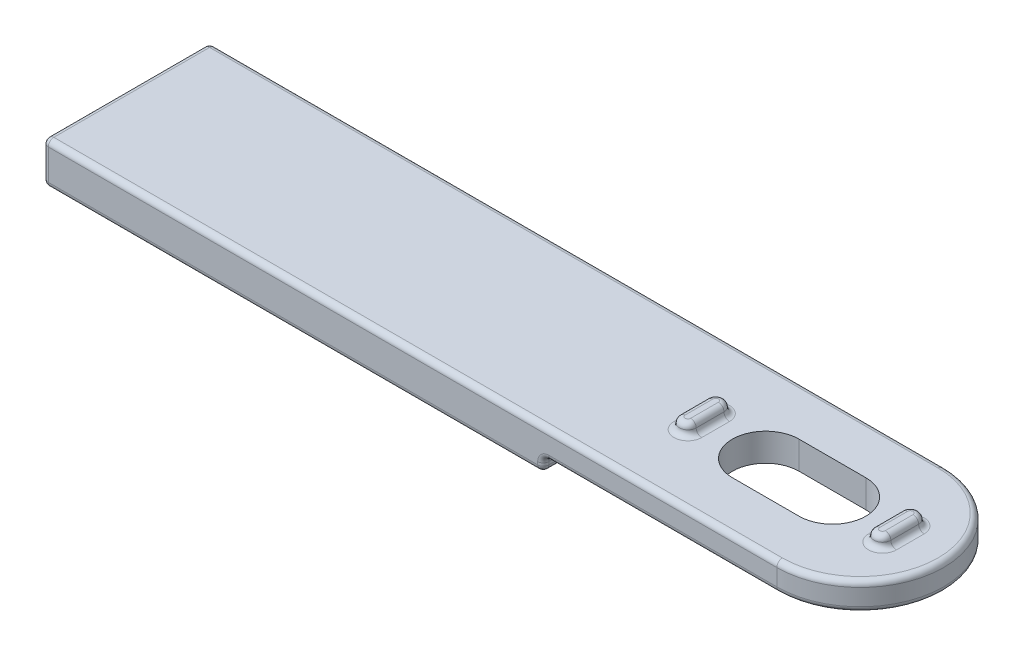
SolidWorks part; units mm, degrees
material "1.0070 (E360)"
ref_plane "Płaszczyzna przednia" through (0, 0, 0) normal (0, 0, 1) x (1, 0, 0)
ref_plane "Płaszczyzna górna" through (0, 0, 0) normal (0, 1, 0) x (1, 0, 0)
ref_plane "Płaszczyzna prawa" through (0, 0, 0) normal (1, 0, 0) x (0, 0, -1)
sketch "Szkic6" plane through (0, 0, -30) normal (0, 1, 0) x (-1, 0, 0)
  line L0 (72.6, 30) -> (-72.6, 30) construction
  line L1 (0, 46.5) -> (0, 13.5) construction
  line L3 (-115, 36) -> (-127, 36)
  line L5 (-115, 24) -> (-127, 24)
  line L8 (-147, 15) -> (0, 15)
  line L9 (0, 15) -> (0, 45)
  line L10 (0, 45) -> (-147, 45)
  line L11 (-147, 45) -> (-147, 15)
  arc A0 (-127, 36) -> (-127, 24) centre (-127, 30) ccw
  arc A2 (-115, 24) -> (-115, 36) centre (-115, 30) ccw
  dimension "D5" = 6
  dimension "D6" = 12
  dimension "D7" = 6
  dimension "D1" = 115
  dimension "D2" = 147
  dimension "D3" = 15
  dimension "D4" = 30
extrude "Dodanie-wyciągnięcie2" add sketch "Szkic6" along normal blind 5 separate body
sketch "Szkic8" plane through (0, 0, 0) normal (0, -1, 0) x (1, 0, 0)
  line L0 (147, -15) -> (0, -15) construction
  line L1 (0, 15) -> (147, 15)
  line L2 (0, 15) -> (0, -15)
  line L3 (0, -15) -> (147, -15)
  line L4 (147, 15) -> (147, -15)
  line L5 (147, 15) -> (147, -15) construction
  line L6 (127, -6) -> (115, -6) construction
  line L7 (115, 6) -> (127, 6) construction
  line L8 (127, -6) -> (115, -6)
  line L9 (115, 6) -> (127, 6)
  arc A0 (115, 6) -> (115, -6) centre (115, 0) ccw construction
  arc A1 (127, -6) -> (127, 6) centre (127, 0) ccw construction
  arc A2 (115, 6) -> (115, -6) centre (115, 0) ccw
  arc A3 (127, -6) -> (127, 6) centre (127, 0) ccw
extrude "Dodanie-wyciągnięcie3" add sketch "Szkic8" along normal blind 2.5
ref_plane "Płaszczyzna1" through (0, -10, 0) normal (0, 1, 0) x (1, 0, 0)
fillet "Zaokrąglenie2" 2 edges at (147, 1.25, 15) (147, 1.25, -15) type full round first side face at (73.5, 1.25, 15) second side face at (73.5, 1.25, -15) middle face at (147, 1.25, 0)
sketch "Szkic9" plane through (0, -2.5, 0) normal (0, 1, 0) x (1, 0, 0)
  line L0 (0, -15) -> (132, -15) construction
  line L1 (90, -15) -> (147, -15)
  line L2 (90, -15) -> (90, 15)
  line L3 (90, 15) -> (147, 15)
  line L4 (147, -15) -> (147, 15)
  line L5 (132, 15) -> (0, 15) construction
  arc A0 (132, -15) -> (132, 15) centre (132, 0) ccw construction
  dimension "D1" = 57
extrude "Wytnij-wyciągnięcie1" cut sketch "Szkic9" along normal blind 2.5
fillet "Zaokrąglenie3" radius 1 16 edges at (90, -1.25, 15) (111, 0, 15) (147, 0, 0) (111, 0, -15) (66, 5, 15) (147, 5, 0) (66, 5, -15) (0, 5, 0) (0, 1.25, 15) (0, 1.25, -15) (0, -2.5, 0) (45, -2.5, 15) (45, -2.5, -15) (90, -2.5, 0) (90, -1.25, -15) (90, 0, 0)
sketch "Szkic10" plane through (0, 5, 0) normal (0, 1, 0) x (1, 0, 0)
  line L1 (103.5, -2.5) -> (103.5, 2.5) construction
  line L2 (102, -2.5) -> (102, 2.5)
  line L3 (105, -2.5) -> (105, 2.5)
  line L4 (121, 0) -> (121, -24.2358) construction
  line L5 (138.5, -2.5) -> (138.5, 2.5) construction
  line L6 (140, -2.5) -> (140, 2.5)
  line L7 (137, -2.5) -> (137, 2.5)
  circle A0 centre (121, 0) radius 16 construction
  arc A1 (102, -2.5) -> (105, -2.5) centre (103.5, -2.5) ccw
  arc A2 (105, 2.5) -> (102, 2.5) centre (103.5, 2.5) ccw
  arc A3 (140, -2.5) -> (137, -2.5) centre (138.5, -2.5) cw
  arc A4 (137, 2.5) -> (140, 2.5) centre (138.5, 2.5) cw
  point P4 (103.5, 0)
  point P14 (138.5, 0)
  dimension "D1" = 32
  dimension "D2" = 6
  dimension "D3" = 3
  dimension "D4" = 5
extrude "Dodanie-wyciągnięcie4" add sketch "Szkic10" along normal blind 2
fillet "Zaokrąglenie4" radius 1 16 edges at (137, 7, 0) (138.5, 7, -4) (140, 7, 0) (137, 5, 0) (138.5, 5, -4) (140, 5, 0) (102, 7, 0) (103.5, 7, -4) (105, 7, 0) (102, 5, 0) (103.5, 5, -4) (105, 5, 0) (138.5, 7, 4) (138.5, 5, 4) (103.5, 7, 4) (103.5, 5, 4)
